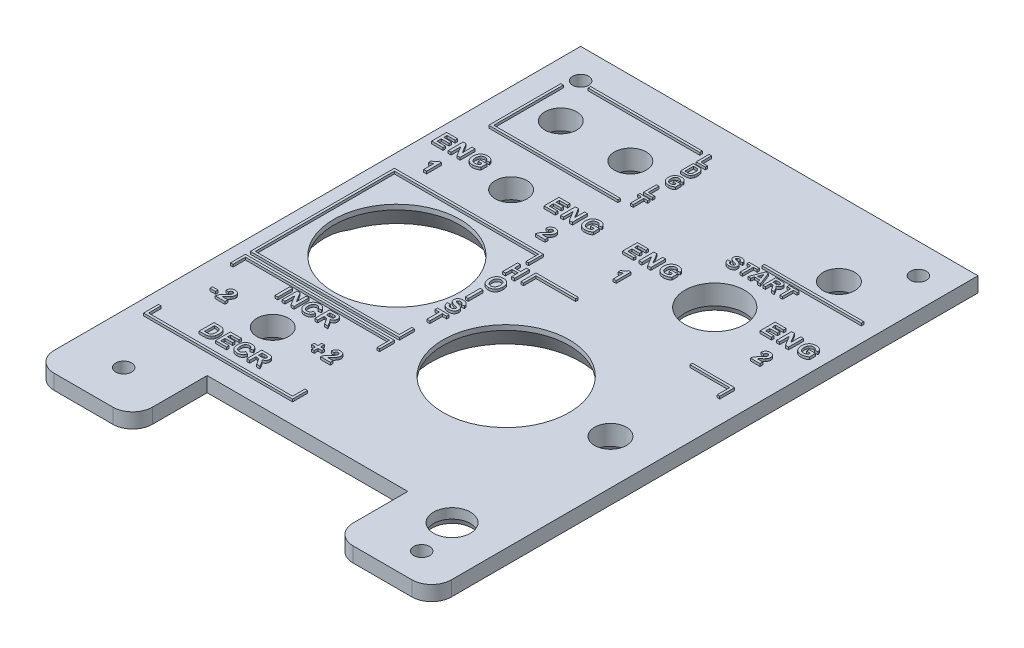
SolidWorks part; units mm, degrees
ref_plane "Спереди" through (0, 0, 0) normal (0, 0, 1) x (1, 0, 0)
ref_plane "Сверху" through (0, 0, 0) normal (0, 1, 0) x (1, 0, 0)
ref_plane "Справа" through (0, 0, 0) normal (1, 0, 0) x (0, 0, -1)
sketch "Sketch1" plane through (0, 0, 0) normal (0, 1, 0) x (1, 0, 0)
  line L1 (40, -55) -> (-40, -55)
  line L2 (40, -55) -> (40, 55)
  line L3 (40, 55) -> (-40, 55)
  line L4 (-40, -55) -> (-40, 55)
  line L5 (40, -55) -> (-40, 55) construction
  line L6 (40, 55) -> (-40, -55) construction
  point P0 (0, 0)
  dimension "D1" = 80
  dimension "D2" = 110
extrude "Boss-Extrude1" add sketch "Sketch1" along normal blind 3
sketch "Sketch2" plane through (0, 0, 55) normal (0, 0, 1) x (1, 0, 0)
  line L0 (0, 3) -> (0, 0) construction
  line L1 (-40, 3) -> (40, 3) construction
  line L2 (-40, 0) -> (40, 0) construction
  line L4 (20.2, 0) -> (-20.2, 0)
  line L5 (20.2, 0) -> (20.2, 3)
  line L6 (20.2, 3) -> (-20.2, 3)
  line L7 (-20.2, 0) -> (-20.2, 3)
  line L8 (20.2, 0) -> (-20.2, 3) construction
  line L9 (20.2, 3) -> (-20.2, 0) construction
  point P6 (0, 1.5)
  dimension "D1" = 40.4
extrude "Cut-Extrude1" cut sketch "Sketch2" against normal blind 15
fillet "Fillet1" radius 4 4 edges at (20.2, 1.5, 55) (40, 1.5, 55) (-20.2, 1.5, 55) (-40, 1.5, 55)
sketch "Sketch7" plane through (0, 0, 0) normal (0, -1, 0) x (1, 0, 0)
  line L0 (-40, -55) -> (-40, 51) construction
  line L1 (40, -55) -> (-40, -55) construction
  line L2 (36.8, 34.8) -> (-36.8, 34.8)
  line L3 (36.8, 34.8) -> (36.8, -51.8)
  line L4 (36.8, -51.8) -> (-36.8, -51.8)
  line L5 (-36.8, 34.8) -> (-36.8, -51.8)
  line L6 (36.8, 34.8) -> (-36.8, -51.8) construction
  line L7 (40, 51) -> (40, -55) construction
  line L8 (36.8, -51.8) -> (-36.8, 34.8) construction
  point P0 (0, -8.5)
  point P11 (0, 34.8)
  point P12 (0, -55)
  dimension "D1" = 3.2
  dimension "D2" = 3.2
  dimension "D3" = 3.2
  dimension "D4" = 89.8
extrude "Boss-Extrude2" add sketch "Sketch7" along normal blind 2
sketch "Sketch3" plane through (0, 3, 0) normal (0, 1, 0) x (1, 0, 0)
  line L0 (-40, 0) -> (40, 0) construction
  line L1 (-40, 55) -> (-40, -51) construction
  line L2 (40, -51) -> (40, 55) construction
  line L3 (-40, -10) -> (40, -10) construction
  line L4 (20.2, -40) -> (-20.2, -40) construction
  circle A0 centre (-22, 0) radius 12.7
  circle A1 centre (10, -10) radius 12.7
  point P10 (0, -10)
  point P13 (0, -40)
  point P16 (0, 0)
  dimension "D1" = 25.4
  dimension "D2" = 30
  dimension "D3" = 40
  dimension "D4" = 18
  dimension "D5" = 30
extrude "Cut-Extrude2" cut sketch "Sketch3" against normal through all
sketch "Sketch4" plane through (0, 3, 0) normal (0, 1, 0) x (1, 0, 0)
  line L0 (40, -51) -> (40, 55) construction
  line L1 (40, 55) -> (-40, 55) construction
  line L2 (19, 55) -> (19, -40) construction
  line L3 (40, -40) -> (-40, -40) construction
  line L4 (-40, 55) -> (-40, -51) construction
  line L5 (20.2, -40) -> (-20.2, -40) construction
  line L6 (40, 23) -> (-40, 23) construction
  line L7 (-22, 0) -> (-22, 55) construction
  line L8 (10, -10) -> (40, -10) construction
  line L9 (20.2, -41) -> (40, -41) construction
  line L10 (20.2, -40) -> (20.2, -51) construction
  line L11 (24.2, -55) -> (36, -55) construction
  line L12 (40, 40) -> (-40, 40) construction
  line L13 (-40, -25) -> (40, -25) construction
  line L15 (-22, 0) -> (-22, -54.3407) construction
  line L16 (-36, -55) -> (-24.2, -55) construction
  line L17 (-40, 49) -> (40, 49) construction
  line L18 (32, -41) -> (32, -55) construction
  line L19 (24.2, -55) -> (36, -55) construction
  circle A0 centre (19, 23) radius 6
  circle A1 centre (-22, 23) radius 3.2
  circle A2 centre (31, -10) radius 3.2
  circle A3 centre (30.1, -41) radius 3.7
  circle A4 centre (-29, 40) radius 3.2
  circle A5 centre (-15, 40) radius 3.2
  circle A6 centre (27, 40) radius 3.2
  circle A7 centre (-22, -25) radius 3.2
  arc A8 (-24.2, -55) -> (-20.2, -51) centre (-24.2, -51) ccw construction
  circle A9 centre (-30, -47) radius 1.6
  circle A10 centre (-34, 49) radius 1.6
  circle A11 centre (34, 49) radius 1.6
  circle A12 centre (32, -49) radius 1.6
  point P12 (0, -40)
  point P61 (0, 49)
  dimension "D1" = 12
  dimension "D7" = 7.4
  dimension "D8" = 14
  dimension "D14" = 6.4
  dimension "D17" = 3.2
  dimension "D20" = 3.2
  dimension "D25" = 3.2
  dimension "D27" = 13
  dimension "D2" = 21
  dimension "D3" = 32
  dimension "D6" = 9
  dimension "D12" = 14
  dimension "D13" = 7
  dimension "D15" = 30
  dimension "D16" = 15
  dimension "D18" = 10
  dimension "D19" = 8
  dimension "D21" = 68
  dimension "D22" = 34
  dimension "D23" = 6
  dimension "D24" = 8
  dimension "D26" = 6
extrude "Cut-Extrude3" cut sketch "Sketch4" against normal through all
chamfer "Chamfer2" distance 1.5 angle 20 4 edges at (36.8, -2, -8.5) (0, -2, -51.8) (-36.8, -2, -8.5) (0, -2, 34.8) first distance on face at (36.8, -1, -8.5) first distance on face at (0, -1, -51.8) first distance on face at (-36.8, -1, -8.5) first distance on face at (0, -1, 34.8)
chamfer "Chamfer3" distance 4 angle 30 2 edges at (-22, -2, 12.7) (10, -2, 22.7) first distance on face at (-22, -2, 12.7) first distance on face at (10, -2, 22.7)
sketch "Sketch8" plane through (0, 3, 0) normal (0, 1, 0) x (1, 0, 0)
  line L0 (-35, 46) -> (-35, 48.5) construction
  line L1 (-35, 48.5) -> (-9, 48.5) construction
  line L2 (-9, 48.5) -> (-9, 46) construction
  line L3 (-9, 46) -> (-9.5, 46) construction
  line L4 (-9.5, 46) -> (-9.5, 48) construction
  line L5 (-9.5, 48) -> (-34.5, 48) construction
  line L6 (-34.5, 48) -> (-34.5, 46) construction
  line L7 (-34.5, 46) -> (-35, 46) construction
  line L8 (-29, 40) -> (-15, 40) construction
  line L9 (31, -10) -> (10, -10) construction
  line L10 (10, -22.7) -> (10, 2.7) construction
  line L11 (-22, 48) -> (-22, 32) construction
  line L12 (-9, 34) -> (-9, 31.5) construction
  line L13 (-9, 31.5) -> (-35, 31.5)
  line L14 (-35, 31.5) -> (-35, 34)
  line L15 (-35, 34) -> (-34.5, 34) construction
  line L16 (-34.5, 34) -> (-34.5, 32)
  line L17 (-34.5, 32) -> (-9.5, 32)
  line L18 (-9.5, 32) -> (-9.5, 34) construction
  line L19 (-9.5, 34) -> (-9, 34) construction
  line L20 (-37, 11.5) -> (-37, 14.5)
  line L21 (-37, 14.5) -> (-7, 14.5)
  line L22 (-7, 14.5) -> (-7, 11.5)
  line L23 (-7, 11.5) -> (-7.5, 11.5)
  line L24 (-7.5, 11.5) -> (-7.5, 14)
  line L25 (-7.5, 14) -> (-36.5, 14)
  line L26 (-36.5, 14) -> (-36.5, 11.5)
  line L27 (-36.5, 11.5) -> (-37, 11.5) construction
  line L28 (-4.5, 7.5) -> (-4.5, 10.5)
  line L29 (-22, 14) -> (-22, -14) construction
  line L30 (-7, -11.5) -> (-7, -14.5)
  line L31 (-7, -14.5) -> (-37, -14.5)
  line L32 (-37, -14.5) -> (-37, -11.5)
  line L33 (-37, -11.5) -> (-36.5, -11.5) construction
  line L34 (-36.5, -11.5) -> (-36.5, -14)
  line L35 (-36.5, -14) -> (-7.5, -14)
  line L36 (-7.5, -14) -> (-7.5, -11.5)
  line L37 (-7.5, -11.5) -> (-7, -11.5)
  line L38 (-22, 12.7) -> (-22, -12.7) construction
  line L39 (-4.5, 10.5) -> (35.5, 10.5) construction
  line L40 (35.5, 10.5) -> (35.5, 7.5)
  line L41 (35.5, 7.5) -> (35, 7.5)
  line L42 (35, 7.5) -> (35, 10)
  line L43 (35, 10) -> (-4, 10) construction
  line L44 (-4, 10) -> (-4, 7.5)
  line L45 (-4, 7.5) -> (-4.5, 7.5)
  line L46 (15.5, 10) -> (15.5, -10) construction
  line L47 (-37, -18.5) -> (-37, -15.5)
  line L48 (-37, -15.5) -> (-7, -15.5)
  line L49 (-7, -15.5) -> (-7, -18.5)
  line L50 (-7, -18.5) -> (-7.5, -18.5)
  line L51 (-7.5, -18.5) -> (-7.5, -16)
  line L52 (-7.5, -16) -> (-36.5, -16)
  line L53 (-36.5, -16) -> (-36.5, -18.5)
  line L54 (-36.5, -18.5) -> (-37, -18.5)
  line L55 (-22, -16) -> (-22, -34) construction
  line L56 (-7, -33) -> (-7, -36)
  line L57 (-7, -36) -> (-37, -36)
  line L58 (-37, -36) -> (-37, -33)
  line L59 (-37, -33) -> (-36.5, -33)
  line L60 (-36.5, -33) -> (-36.5, -35.5)
  line L61 (-36.5, -35.5) -> (-7.5, -35.5)
  line L62 (-7.5, -35.5) -> (-7.5, -33)
  line L63 (-7.5, -33) -> (-7, -33)
  line L64 (-78.7082, -66.728) -> (-78.7082, -92.128) construction
  line L65 (-18.8, -25) -> (-25.2, -25) construction
  line L66 (-35, 46) -> (-35, 34)
  line L67 (-34.5, 46) -> (-34.5, 34)
  line L68 (-9, 48.5) -> (-9, 48)
  line L69 (-9, 48) -> (-9.5, 48)
  line L70 (-9.5, 32) -> (-9, 32)
  line L71 (-9, 32) -> (-9, 31.5)
  line L72 (-37, -11.5) -> (-37, 11.5)
  line L73 (-36.5, 11.5) -> (-36.5, -11.5)
  line L74 (-22, -25) -> (-22, -35.5) construction
  line L75 (20.2, -40) -> (-20.2, -40) construction
  line L76 (40, -51) -> (40, 55) construction
  line L77 (37, 34.5) -> (17, 34.5)
  line L78 (37, 34.5) -> (37, 35)
  line L79 (37, 35) -> (17, 35)
  line L80 (17, 34.5) -> (17, 35)
  line L81 (37, 34.5) -> (17, 35) construction
  line L82 (37, 35) -> (17, 34.5) construction
  line L83 (40, 55) -> (-40, 55) construction
  line L84 (-35, 46) -> (-34.5, 46)
  line L85 (-31.5, 48.5) -> (-31.5, 48)
  line L86 (-31.5, 48) -> (-9.5, 48)
  line L87 (-9, 48.5) -> (-31.5, 48.5)
  line L88 (-4.5, 10.5) -> (4, 10.5)
  line L89 (4, 10.5) -> (4, 10)
  line L90 (4, 10) -> (-4, 10)
  line L91 (27, 10.5) -> (27, 10)
  line L92 (27, 10) -> (35, 10)
  line L93 (35.5, 10.5) -> (27, 10.5)
  circle A1 centre (-22, 0) radius 12.7 construction
  circle A2 centre (10, -10) radius 12.7 construction
  circle A3 centre (-22, -25) radius 3.2 construction
  point P12 (-22, 40)
  point P15 (-22, 32)
  point P39 (-22, -14)
  point P51 (-22, 0)
  point P64 (-22, 0)
  point P66 (20.5, -10)
  point P95 (-22, -25)
  point P96 (-22, -25)
  point P102 (27, 34.75)
  dimension "D14" = 4
  dimension "D1" = 0.5
  dimension "D2" = 0.5
  dimension "D3" = 26
  dimension "D4" = 2
  dimension "D5" = 16
  dimension "D6" = 30
  dimension "D7" = 28
  dimension "D8" = 40
  dimension "D9" = 5
  dimension "D10" = 20
  dimension "D11" = 9
  dimension "D12" = 0.5
  dimension "D13" = 0.5
  dimension "D15" = 20
  dimension "D16" = 3
  dimension "D17" = 20
  dimension "D18" = 3
  dimension "D19" = 23
  dimension "D20" = 0.5
  dimension "D21" = 0.5
  dimension "D22" = 0.5
chamfer "Chamfer4" distance 1 angle 20 8 edges at (30.1, 0, 44.7) (31, -2, 13.2) (-22, -2, 28.2) (-22, -2, -19.8) (-29, -2, -36.8) (-15, -2, -36.8) (19, -2, -17) (27, -2, -36.8) first distance on face at (30.1, 3, 44.7) first distance on face at (31, -2, 13.2) first distance on face at (-22, -2, 28.2) first distance on face at (-22, -2, -19.8) first distance on face at (-29, -2, -36.8) first distance on face at (-15, -2, -36.8) first distance on face at (19, -2, -17) first distance on face at (27, -2, -36.8)
sketch "Sketch9" plane through (0, 3, 0) normal (0, 1, 0) x (1, 0, 0)
  line L0 (-8, 48) -> (-8, 32) construction
  line L1 (-40, 55) -> (-40, -51) construction
  text T0 "<b><r90>  L D G L T</r></b>" font "Arial" height 2.6
  dimension "D1" = 32
sketch "Sketch11" plane through (0, 3, 0) normal (0, 1, 0) x (1, 0, 0)
  line L0 (40, 31.2) -> (0, 31.2) construction
  line L1 (40, -51) -> (40, 55) construction
  line L2 (40, 55) -> (-40, 55) construction
  line L3 (40, 23) -> (-40, 23) construction
  line L4 (-40, 55) -> (-40, -51) construction
  text T0 "<b>          START</b>" font "Arial" height 2.6
  text T1 "<b> ENG       ENG   ENG          ENG</b>\r\n   <b>1            2  </b>   <b>  1               2  </b>" font "Arial" height 3
  dimension "D1" = 40
  dimension "D2" = 23.8
  dimension "D3" = 32
sketch "Sketch13" plane through (0, 3, 0) normal (0, 1, 0) x (1, 0, 0)
  line L0 (-8.4, 12) -> (-8.4, -12) construction
  line L1 (-40, -0.8) -> (40, -0.8) construction
  line L2 (-40, 55) -> (-40, -51) construction
  line L3 (40, -51) -> (40, 55) construction
  line L4 (40, 55) -> (-40, 55) construction
  text T0 "<b>    <r90>H O    S T</r></b>" font "Arial" height 3
  text T1 "<b>                            I</b>" font "Arial" height 3
  dimension "D1" = 31.6
  dimension "D2" = 55.8
sketch "Sketch15" plane through (0, 3, 0) normal (0, 1, 0) x (1, 0, 0)
  line L0 (-40, -19.7) -> (40, -19.7) construction
  line L1 (-40, 55) -> (-40, -51) construction
  line L2 (40, -51) -> (40, 55) construction
  line L3 (40, -33.56) -> (-40, -33.56) construction
  line L6 (-18.8, -25) -> (-25.2, -25) construction
  line L7 (-40, -25.7935) -> (40, -25.7935) construction
  circle A0 centre (-22, -25) radius 3.2 construction
  text T0 "<b>         INCR</b>" font "Arial" height 3
  text T1 "<b>        DECR</b>" font "Arial" height 3
  text T2 "<b>   -2         +2</b>" font "Arial" height 3
  dimension "D1" = 5.3
  dimension "D2" = 8.56
sketch "Sketch16" plane through (0, 3, 0) normal (0, 1, 0) x (1, 0, 0)
  circle A0 centre (-15, 40) radius 4.5
  circle A1 centre (-29, 40) radius 4.5
  circle A2 centre (31, -10) radius 4.5
  circle A3 centre (-22, -25) radius 4.5
  circle A4 centre (-22, 23) radius 4.5
  circle A5 centre (30.1, -41) radius 4.5
  circle A6 centre (27, 40) radius 4.5
  circle A7 centre (19, 23) radius 8.5
  dimension "D1" = 9
  dimension "D2" = 17
extrude "Boss-Extrude3" add sketch "Sketch8" along normal blind 0.5
extrude "Boss-Extrude4" add sketch "Sketch9" along normal blind 0.5
extrude "Boss-Extrude5" add sketch "Sketch11" along normal blind 0.5
extrude "Boss-Extrude6" add sketch "Sketch13" along normal blind 0.5
extrude "Boss-Extrude7" add sketch "Sketch15" along normal blind 0.5
